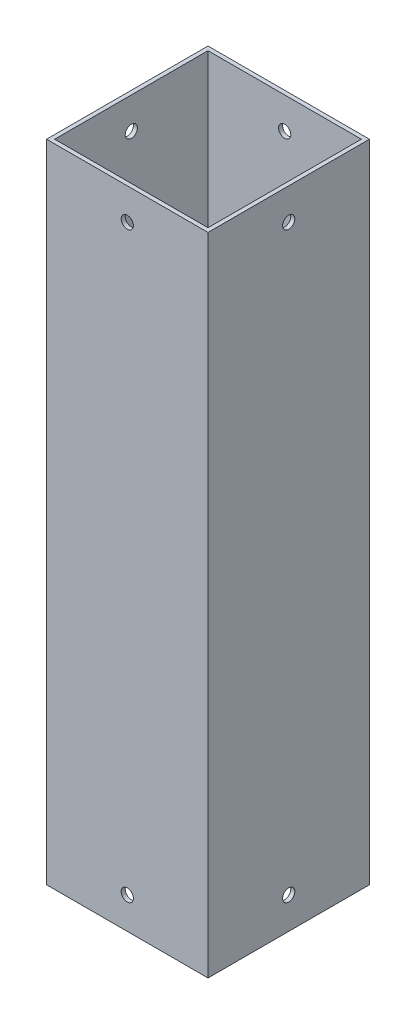
SolidWorks part; units mm, degrees
material "6061 Alloy"
ref_plane "Front Plane" through (0, 0, 0) normal (0, 0, 1) x (1, 0, 0)
ref_plane "Top Plane" through (0, 0, 0) normal (0, 1, 0) x (1, 0, 0)
ref_plane "Right Plane" through (0, 0, 0) normal (1, 0, 0) x (0, 0, -1)
sketch "Sketch1" plane through (0, 0, 0) normal (0, 1, 0) x (1, 0, 0)
  line L1 (-30.1625, 30.1625) -> (30.1625, 30.1625)
  line L2 (-30.1625, 30.1625) -> (-30.1625, -30.1625)
  line L3 (-30.1625, -30.1625) -> (30.1625, -30.1625)
  line L4 (30.1625, 30.1625) -> (30.1625, -30.1625)
  line L5 (-31.75, 31.75) -> (31.75, 31.75)
  line L6 (-31.75, 31.75) -> (-31.75, -31.75)
  line L7 (-31.75, -31.75) -> (31.75, -31.75)
  line L8 (31.75, 31.75) -> (31.75, -31.75)
  point P2 (-31.75, 0)
  point P11 (-30.1625, 0)
  point P12 (0, 30.1625)
  point P13 (0, 31.75)
  dimension "D1" = 60.325
  dimension "1.95" = 60.325
  dimension "2.05" = 63.5
  dimension "D2" = 63.5
extrude "Boss-Extrude1" add sketch "Sketch1" along normal blind 254
ref_plane "Plane1" through (0, 152.4, 0) normal (0, 1, 0) x (1, 0, 0)
sketch "Sketch3" plane through (0, 152.4, 0) normal (0, 1, 0) x (1, 0, 0)
  line L1 (-30.1625, 30.1625) -> (30.1625, 30.1625)
  line L2 (-30.1625, 30.1625) -> (-30.1625, -30.1625)
  line L3 (-30.1625, -30.1625) -> (30.1625, -30.1625)
  line L4 (30.1625, 30.1625) -> (30.1625, -30.1625)
extrude "Boss-Extrude3" add sketch "Sketch3" against normal blind 2.54
sketch "Sketch4" plane through (-30.1625, 0, 0) normal (1, 0, 0) x (0, 0, -1)
  line L0 (-31.75, 254) -> (31.75, 254) construction
  line L1 (31.75, 254) -> (31.75, 0) construction
  circle A0 centre (0, 241.5876) radius 2.4
  dimension "D1" = 4.8
  dimension "D2" = 12.4124
  dimension "D3" = 31.75
extrude "Cut-Extrude1" cut sketch "Sketch4" along normal through all both and the other way through all
sketch "Sketch5" plane through (0, 0, -31.75) normal (0, 0, -1) x (-1, 0, 0)
  line L0 (-31.75, 254) -> (31.75, 254) construction
  line L1 (31.75, 254) -> (31.75, 0) construction
  circle A0 centre (0, 241.5876) radius 2.4
  dimension "D1" = 4.8
  dimension "D2" = 12.4124
  dimension "D3" = 31.75
extrude "Cut-Extrude2" cut sketch "Sketch5" against normal through all
sketch "Sketch6" plane through (31.75, 0, 0) normal (1, 0, 0) x (0, 0, -1)
  line L0 (-31.75, 0) -> (31.75, 0) construction
  line L1 (31.75, 254) -> (31.75, 0) construction
  circle A0 centre (0, 12.4124) radius 2.4
  dimension "D1" = 12.4124
  dimension "D2" = 4.8
  dimension "D3" = 31.75
extrude "Cut-Extrude3" cut sketch "Sketch6" against normal through all both and the other way through all
sketch "Sketch7" plane through (0, 0, -31.75) normal (0, 0, -1) x (-1, 0, 0)
  line L0 (-31.75, 0) -> (31.75, 0) construction
  circle A0 centre (0, 12.4124) radius 2.4
  dimension "D1" = 4.8
  dimension "D2" = 12.4124
  dimension "D3" = 31.75
extrude "Cut-Extrude4" cut sketch "Sketch7" against normal through all both
equation "\"1.95@Sketch1\"=2.5-(1/8)"
equation "\"D1@Sketch1\"=\"1.95@Sketch1\""
